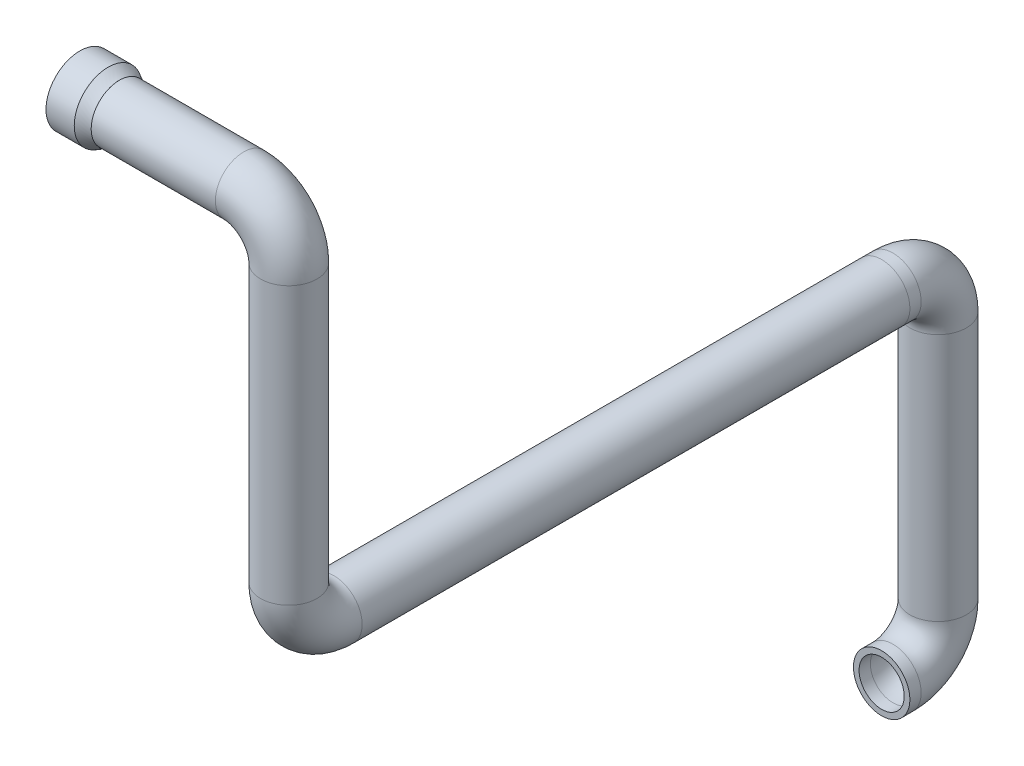
SolidWorks part; units mm, degrees
ref_plane "Front Plane" through (0, 0, 0) normal (0, 0, 1) x (1, 0, 0)
ref_plane "Top Plane" through (0, 0, 0) normal (0, 1, 0) x (1, 0, 0)
ref_plane "Right Plane" through (0, 0, 0) normal (1, 0, 0) x (0, 0, -1)
sketch "Sketch1" plane through (0, 0, 0) normal (0, 0, 1) x (1, 0, 0)
  circle A0 centre (0, 0) radius 5
  circle A1 centre (0, 0) radius 4
  dimension "D1" = 10
  dimension "D2" = 8
sketch "Sketch2" plane through (0, 0, 0) normal (1, 0, 0) x (0, 0, -1)
  line L0 (0, 0) -> (2, 0)
  line L1 (10, 8) -> (10, 52)
  line L2 (2, 60) -> (0, 60)
  line L3 (0, 60) -> (-97, 60)
  line L4 (-105, 68) -> (-105, 115)
  arc A0 (10, 52) -> (2, 60) centre (2, 52) ccw
  arc A1 (2, 0) -> (10, 8) centre (2, 8) ccw
  arc A2 (-97, 60) -> (-105, 68) centre (-97, 68) cw
  point P8 (10, 60)
  point P11 (10, 0)
  point P15 (-105, 60)
  dimension "D5" = 8
  dimension "D7" = 8
  dimension "D1" = 10
  dimension "D2" = 60
  dimension "D3" = 10
  dimension "D4" = 105
  dimension "D6" = 55
sweep "Sweep1" add profiles "Sketch1" path "Sketch2"
ref_point "Point1"
ref_plane "Plane1" through (0, 0, 105) normal (0, 0, -1) x (-1, 0, 0)
sketch "Sketch4" plane through (0, 0, 105) normal (0, 0, -1) x (-1, 0, 0)
  line L0 (0, 115) -> (0, 117)
  line L2 (8, 125) -> (10, 125)
  arc A1 (0, 117) -> (8, 125) centre (8, 117) cw
  point P8 (0, 125)
  dimension "D1" = 10
  dimension "D3" = 2
  dimension "D2" = 8
sketch "Sketch5" plane through (0, 115, 0) normal (0, 1, 0) x (1, 0, 0)
  circle A2 centre (0, -105) radius 4
  circle A3 centre (0, -105) radius 4
  circle A5 centre (0, -105) radius 5
  circle A6 centre (0, -105) radius 5
  dimension "D1" = 1
  dimension "D2" = 0
sweep "Sweep2" add profiles "Sketch5" path "Sketch4"
sketch "Sketch6" plane through (-10, 0, 0) normal (-1, 0, 0) x (0, 0, 1)
  circle A3 centre (105, 125) radius 5
  circle A4 centre (105, 125) radius 4
  dimension "D2" = 1
extrude "Boss-Extrude2" add sketch "Sketch6" along normal blind 20
sketch "Sketch7" plane through (-30, 0, 0) normal (-1, 0, 0) x (0, 0, 1)
  circle A0 centre (105, 125) radius 4
  circle A1 centre (105, 125) radius 5
ref_plane "Plane2" through (-32, 0, 0) normal (-1, 0, 0) x (0, 0, 1)
sketch "Sketch8" plane through (-32, 0, 0) normal (-1, 0, 0) x (0, 0, 1)
  circle A0 centre (105, 125) radius 5
  circle A1 centre (105, 125) radius 6
loft "Loft1" add section "Sketch7" section "Sketch8" connector at (-30, 125.6267, 109.9606) connector at (-32, 127.2822, 110.549)
sketch "Sketch9" plane through (-32, 0, 0) normal (-1, 0, 0) x (0, 0, 1)
  circle A0 centre (105, 125) radius 6
extrude "Boss-Extrude3" add sketch "Sketch9" along normal blind 5
sketch "Sketch10" plane through (-37, 0, 0) normal (-1, 0, 0) x (0, 0, 1)
  circle A0 centre (105, 125) radius 5
  dimension "D1" = 10
extrude "Cut-Extrude1" cut sketch "Sketch10" against normal blind 5
sketch "Sketch11" plane through (-32, 0, 0) normal (-1, 0, 0) x (0, 0, 1)
  circle A0 centre (105, 125) radius 4
  dimension "D1" = 8
extrude "Cut-Extrude2" cut sketch "Sketch11" against normal blind 5
